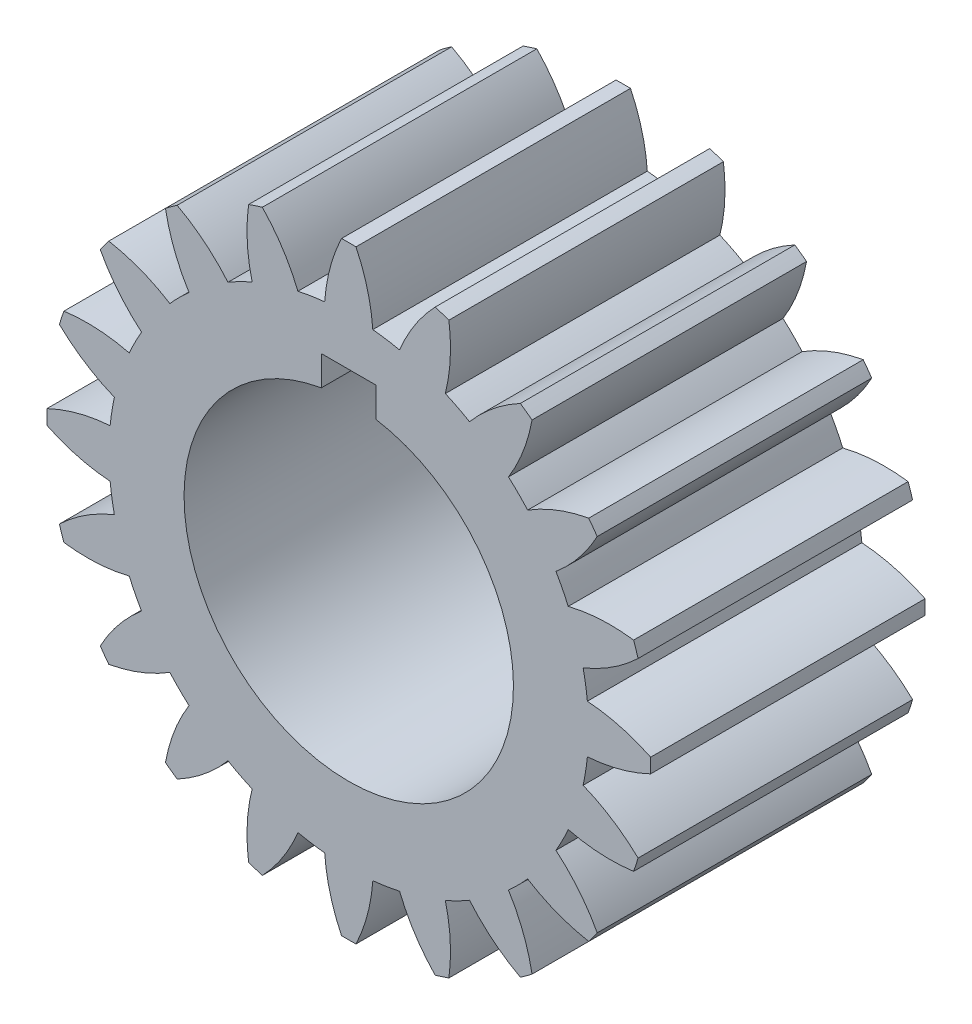
SolidWorks part; units mm, degrees
ref_plane "Front Plane" through (0, 0, 0) normal (0, 0, 1) x (1, 0, 0)
ref_plane "Top Plane" through (0, 0, 0) normal (0, 1, 0) x (1, 0, 0)
ref_plane "Right Plane" through (0, 0, 0) normal (1, 0, 0) x (0, 0, -1)
sketch "Sketch1" plane through (0, 0, 0) normal (0, 1, 0) x (1, 0, 0)
  line L0 (0, 0) -> (0, 23.1781) construction
  line L2 (18, 30) -> (26.21, 30)
  line L3 (18, 30) -> (18, 0)
  line L4 (18, 0) -> (26.21, 0)
  line L5 (26.21, 30) -> (26.21, 0)
  line L6 (18, 30) -> (26.21, 0) construction
  line L7 (18, 0) -> (26.21, 30) construction
  point P3 (22.105, 15)
  point P8 (0, 0)
  dimension "D1" = 18
  dimension "D2" = 30
  dimension "D3" = 26.21
revolve "Revolve1" add sketch "Sketch1" angle 360 about L0
sketch "Sketch2" plane through (0, 0, 0) normal (0, 0, 1) x (1, 0, 0)
  line L0 (0, 0) -> (0, 26.21) construction
  circle A0 centre (0, 0) radius 26.21 construction
  circle A1 centre (0, 0) radius 33
  circle A2 centre (0, 0) radius 26.21
  arc A3 (-2.63, 26.0777) -> (-0.79, 32.9905) centre (16.3596, 24.7245) cw
  arc A4 (2.63, 26.0777) -> (0.79, 32.9905) centre (-16.3596, 24.7245) ccw
  point P13 (0, 0)
  point P14 (0, 0)
  circle M2 centre (0, 0) radius 26.21
  dimension "D1" = 66
  dimension "D2" = 1.58
  dimension "D3" = 5.26
extrude "Boss-Extrude1" add sketch "Sketch2" against normal up to surface (30 mm away) contours A2 A4 A1 A3 M2 region at (0, 29.0449, 0) up to face at (18, 0, -30)
ref_axis "Axis1" through (0, 0, -30) along (0, 0, 1)
pattern_circular "CirPattern1" count 20 over 360 about axis through (0, 0, -30) along (0, 0, 1) of "Boss-Extrude1"
sketch "Sketch3" plane through (0, 0, 0) normal (0, 0, 1) x (1, 0, 0)
  line L1 (3, 21) -> (-3, 21)
  line L2 (3, 21) -> (3, 15)
  line L3 (3, 15) -> (-3, 15)
  line L4 (-3, 21) -> (-3, 15)
  line L5 (3, 21) -> (-3, 15) construction
  line L6 (3, 15) -> (-3, 21) construction
  circle A0 centre (0, 0) radius 18 construction
  point P0 (0, 18)
  dimension "D1" = 6
extrude "Cut-Extrude1" cut sketch "Sketch3" against normal through all
